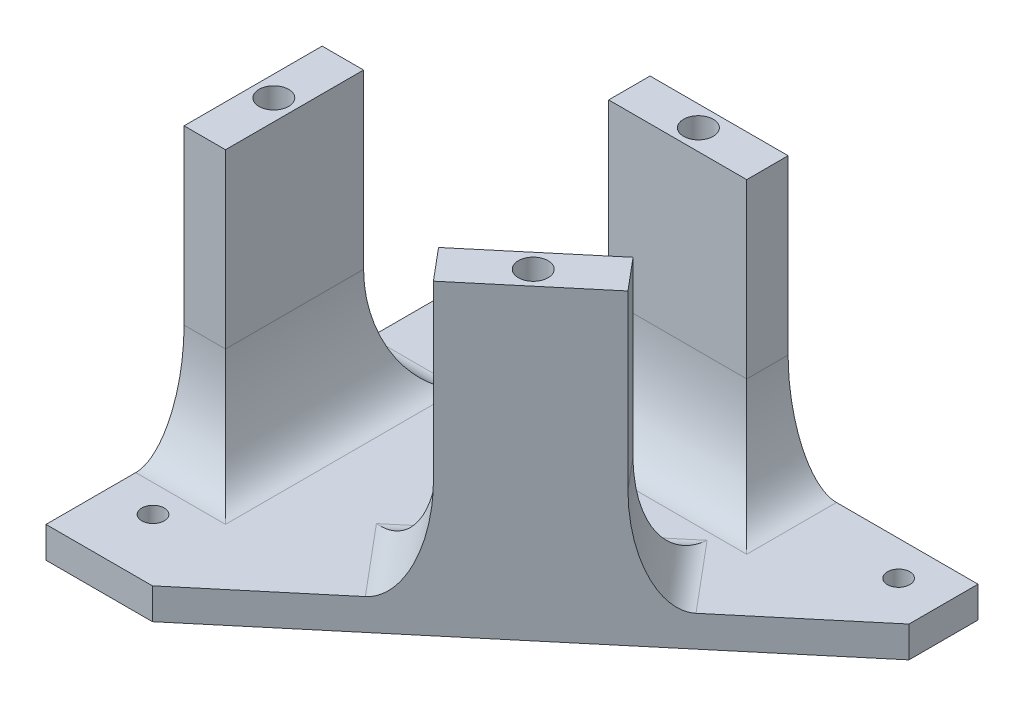
SolidWorks part; units mm, degrees
ref_plane "Front Plane" through (0, 0, 0) normal (0, 0, 1) x (1, 0, 0)
ref_plane "Top Plane" through (0, 0, 0) normal (0, 1, 0) x (1, 0, 0)
ref_plane "Right Plane" through (0, 0, 0) normal (1, 0, 0) x (0, 0, -1)
sketch "Sketch1" plane through (0, 0, 0) normal (0, 1, 0) x (1, 0, 0)
  line L0 (37.5, 60) -> (37.5, 18.5338) construction
  line L1 (15.4123, 0) -> (0, 0)
  line L2 (75, 50) -> (75, 60)
  line L3 (75, 60) -> (0, 60)
  line L4 (0, 0) -> (0, 60)
  line L5 (68.5, 55) -> (6.5, 55) construction
  line L6 (6.5, 55) -> (6.5, 9) construction
  line L7 (75, 50) -> (15.4123, 0)
  circle A0 centre (68.5, 55) radius 1.625
  circle A1 centre (6.5, 55) radius 1.625
  circle A2 centre (6.5, 9) radius 1.625
  point P4 (-12.3674, 12.7654)
  point P8 (75, 48.9369)
  dimension "D3" = 3.25
  dimension "D5" = 60
  dimension "D1" = 31
  dimension "D2" = 75
  dimension "D4" = 46
  dimension "D6" = 5
  dimension "D7" = 140
  dimension "D8" = 10
extrude "Boss-Extrude1" add sketch "Sketch1" along normal blind 4.5
sketch "Sketch2" plane through (0, 4.5, 0) normal (0, 1, 0) x (1, 0, 0)
  line L0 (75, 60) -> (0, 60) construction
  line L1 (47.5, 60) -> (27.5, 60)
  line L2 (47.5, 60) -> (47.5, 54)
  line L3 (47.5, 54) -> (27.5, 54)
  line L4 (27.5, 60) -> (27.5, 54)
  line L5 (0, 60) -> (0, 0) construction
  line L6 (0, 40) -> (6, 40)
  line L7 (0, 40) -> (0, 20)
  line L8 (0, 20) -> (6, 20)
  line L9 (6, 40) -> (6, 20)
  line L10 (52.8666, 31.4279) -> (37.5457, 18.5721)
  line L11 (15.4123, 0) -> (75, 50) construction
  line L12 (37.5457, 18.5721) -> (33.689, 23.1684)
  line L13 (33.689, 23.1684) -> (49.0099, 36.0241)
  line L14 (49.0099, 36.0241) -> (52.8666, 31.4279)
  point P18 (37.5, 60)
  point P19 (0, 30)
  point P20 (45.2062, 25)
  dimension "D1" = 6
  dimension "D2" = 6
  dimension "D3" = 6
  dimension "D4" = 20
  dimension "D5" = 20
  dimension "D6" = 20
extrude "Boss-Extrude2" add sketch "Sketch2" along normal blind 40
sketch "Sketch3" plane through (0, 44.5, 0) normal (0, 1, 0) x (1, 0, 0)
  line L1 (6, 20) -> (6, 40) construction
  line L2 (6, 40) -> (0, 40) construction
  line L3 (27.5, 54) -> (47.5, 54) construction
  line L4 (47.5, 54) -> (47.5, 60) construction
  line L5 (50.9382, 33.726) -> (35.6174, 20.8703) construction
  line L6 (52.8666, 31.4279) -> (49.0099, 36.0241) construction
  line L7 (33.689, 23.1684) -> (37.5457, 18.5721) construction
  circle A0 centre (3, 30) radius 2.15
  circle A1 centre (37.5, 57) radius 2.15
  circle A2 centre (43.2778, 27.2981) radius 2.15
  point P6 (43.2778, 27.2981)
  point P10 (6, 30)
  point P13 (3, 40)
  point P16 (37.5, 54)
  point P19 (47.5, 57)
  dimension "D1" = 4.3
extrude "Cut-Extrude1" cut sketch "Sketch3" against normal blind 5
fillet "Fillet1" radius 7 9 edges at (50.9382, 4.5, -33.726) (3, 4.5, -40) (35.6174, 4.5, -20.8703) (3, 4.5, -20) (27.5, 4.5, -57) (47.5, 4.5, -57) (41.3494, 4.5, -29.5963) (37.5, 4.5, -54) (6, 4.5, -30) second distance 15 first distance on face at (6.5, 4.5, -56.625)
